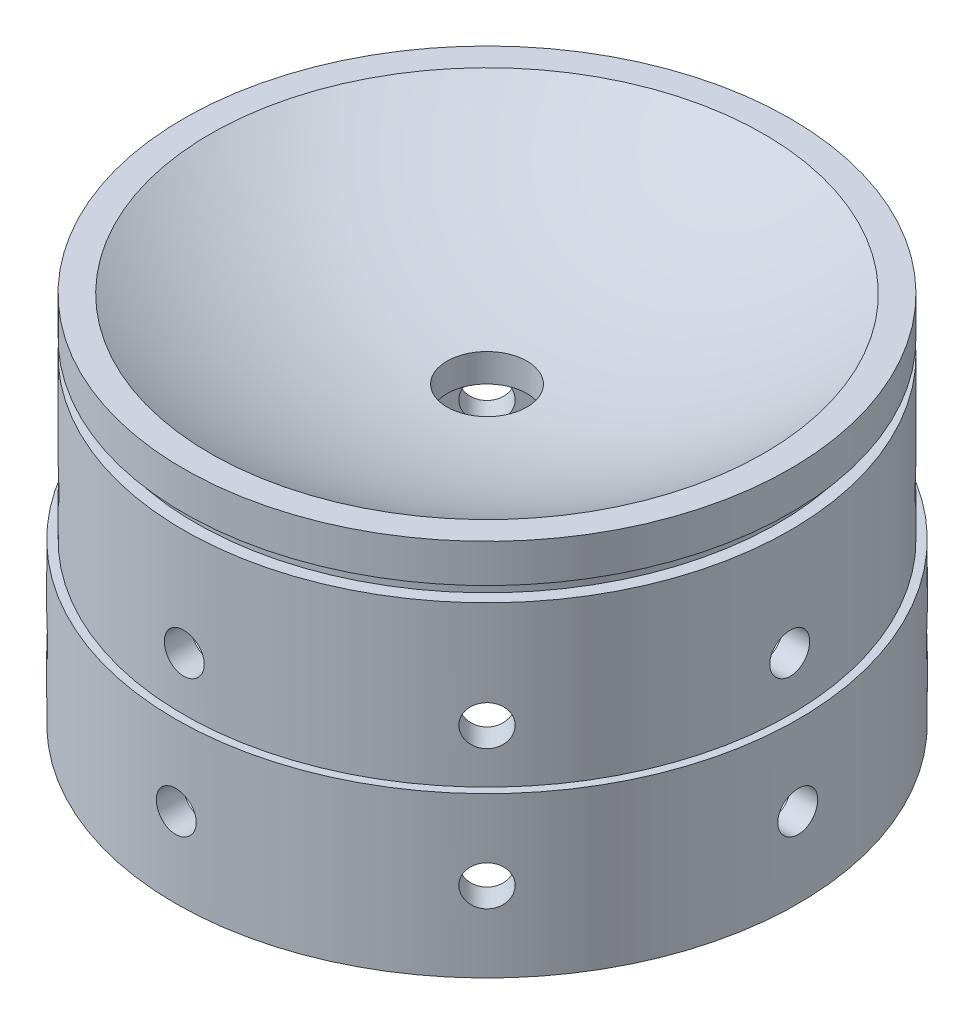
SolidWorks part; units mm, degrees
material "6061-T6 (SS)"
ref_plane "Front Plane" through (0, 0, 0) normal (0, 0, 1) x (1, 0, 0)
ref_plane "Top Plane" through (0, 0, 0) normal (0, 1, 0) x (1, 0, 0)
ref_plane "Right Plane" through (0, 0, 0) normal (1, 0, 0) x (0, 0, -1)
sketch "Sketch1" plane through (0, 0, 0) normal (0, 0, 1) x (1, 0, 0)
  line L0 (0, 0) -> (0, 6.35)
  line L1 (0, 0) -> (72.39, 0)
  line L2 (72.39, 0) -> (72.39, 12.7)
  line L3 (72.39, 12.7) -> (69.469, 12.7)
  line L4 (69.469, 12.7) -> (69.469, 16.256)
  line L5 (69.469, 16.256) -> (72.39, 16.256)
  line L6 (72.39, 16.256) -> (72.39, 25.4)
  line L9 (72.39, 6.35) -> (0, 6.35) construction
  line L10 (72.39, 0) -> (72.39, -25.4)
  line L11 (72.39, -25.4) -> (66.04, -25.4)
  line L12 (66.04, -25.4) -> (66.04, 0)
  line L13 (74.93, 68.1653) -> (74.93, 53.6699) construction
  line L14 (67.945, -63.5) -> (67.945, -25.4)
  line L15 (67.945, -63.5) -> (74.295, -63.5)
  line L16 (9.525, 6.7164) -> (9.525, 0)
  line L17 (73.025, 45.3691) -> (73.025, 21.7883) construction
  line L18 (74.295, -63.5) -> (74.295, -25.4)
  line L19 (74.295, -25.4) -> (72.39, -25.4)
  line L20 (72.39, 25.4) -> (66.04, 25.4)
  arc A1 (0, 6.35) -> (66.04, 25.4) centre (0, 130.3443) ccw
  dimension "D1" = 72.39
  dimension "D9" = 6.35
  dimension "D12" = 9.525
  dimension "D3" = 12.7
  dimension "D4" = 3.556
  dimension "D2" = 73.025
  dimension "D13" = 3.556
  dimension "D6" = 6.35
  dimension "D7" = 25.4
  dimension "D8" = 74.93
  dimension "D10" = 38.1
  dimension "D11" = 74.295
  dimension "D5" = 25.4
  dimension "D14" = 6.35
revolve "Revolve1" add sketch "Sketch1" angle 360 about L0 region at (48.3195, 8.6296, 0) region at (69.215, -12.7, 0) region at (71.12, -44.45, 0)
hole_wizard "3/8 (0.375) Diameter Hole1" positions "3DSketch5" profile "Sketch8" hole size "3/8" standard "ANSI Inch"
sketch3d "3DSketch5"
  line L0 (0, -25.4, 0) -> (0, 0, 0) construction
  line L2 (0, -12.7, 0) -> (72.39, -12.7, 0)
  circle A8 centre (0, -25.4, 0) radius 72.39 construction
  circle A9 centre (0, -25.4, 0) radius 72.39
  point P0 (72.39, -12.7, 0)
  point P41 (0, -97.79, 0)
  point P43 (0, -97.79, 0)
  point P53 (72.39, -12.7, 0)
sketch "Sketch8" plane through (72.39, -12.7, 0) normal (0, 1, 0) x (0, 0, -1)
  line L0 (0, 0) -> (0, 75.2506)
  line L1 (0, 75.2506) -> (4.7625, 72.389)
  line L2 (4.7625, 72.389) -> (4.7625, 0)
  line L5 (4.7625, 0) -> (0, 0)
  line L10 (0, 75.2506) -> (-4.7625, 72.389) construction
  line L11 (0, -6.35) -> (0, 107.95) construction
  dimension "Hole Dia." = 9.525
  dimension "Hole Depth" = 72.389
  dimension "Drill Angle" = 118
hole_wizard "3/8 (0.375) Diameter Hole2" positions "3DSketch6" profile "Sketch9" hole size "3/8" standard "ANSI Inch"
sketch3d "3DSketch6"
  line L0 (0, -25.4, 0) -> (0, -63.5, 0)
  line L2 (0, -44.45, 0) -> (74.295, -44.45, 0)
  circle A0 centre (0, -63.5, 0) radius 74.295 construction
  circle A1 centre (0, -25.4, 0) radius 74.295 construction
  circle A2 centre (0, -63.5, 0) radius 74.295
  circle A3 centre (0, -25.4, 0) radius 74.295
  point P0 (74.295, -44.45, 0)
  point P5 (0, -137.795, 0)
  point P8 (0, -99.695, 0)
  point P10 (0, -137.795, 0)
  point P12 (0, -99.695, 0)
sketch "Sketch9" plane through (74.295, -44.45, 0) normal (0, 1, 0) x (0, 0, -1)
  line L0 (0, 0) -> (0, 77.1556)
  line L1 (0, 77.1556) -> (4.7625, 74.294)
  line L2 (4.7625, 74.294) -> (4.7625, 0)
  line L5 (4.7625, 0) -> (0, 0)
  line L10 (0, 77.1556) -> (-4.7625, 74.294) construction
  line L11 (0, -6.35) -> (0, 107.95) construction
  dimension "Hole Dia." = 9.525
  dimension "Hole Depth" = 74.294
  dimension "Drill Angle" = 118
ref_axis "CenterAxis" through (0, 6.7164, 0) along (0, -1, 0)
chamfer "Chamfer1" distance 2.54 angle 45 1 edges at (0, -25.4, -67.945)
pattern_circular "CirPattern1" count 8 over 360 about axis through (0, -25.4, 0) along (0, -1, 0) of "3/8 (0.375) Diameter Hole1", "3/8 (0.375) Diameter Hole2"
equation "\"D1@Sketch1\"=(5.75/2)-(0.025in)"
equation "\"D12@Sketch1\"=0.75/2"
equation "\"D2@Sketch1\"=5.75/2"
equation "\"D8@Sketch1\"=5.9/2"
equation "\"D11@Sketch1\"=5.9/2 - (0.025in)"
